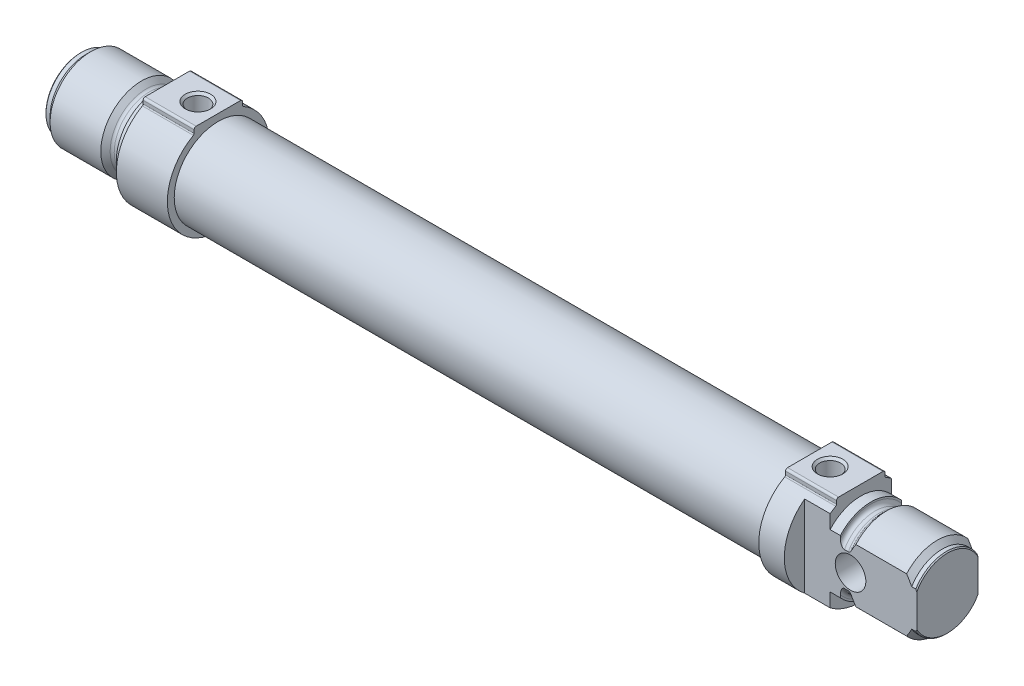
SolidWorks part; units mm, degrees
ref_plane "Ebene vorne" through (0, 0, 0) normal (0, 0, 1) x (1, 0, 0)
ref_plane "Ebene oben" through (0, 0, 0) normal (0, 1, 0) x (1, 0, 0)
ref_plane "Ebene rechts" through (0, 0, 0) normal (1, 0, 0) x (0, 0, -1)
sketch "Skizze1" plane through (0, 0, 0) normal (0, 0, 1) x (1, 0, 0)
  line L0 (0, 0) -> (0, 6.8)
  line L1 (0, 6.8) -> (0.2, 7)
  line L2 (0.2, 7) -> (1, 7)
  line L3 (1, 7) -> (2, 8)
  line L4 (2, 8) -> (11.95, 8)
  line L5 (11.95, 8) -> (12.8657, 7.0843)
  line L6 (13.4314, 6.85) -> (14.2, 6.85)
  line L7 (15, 7.65) -> (15, 8)
  line L8 (15, 8) -> (17, 8)
  line L9 (17, 8) -> (17, 0)
  line L10 (17, 0) -> (0, 0)
  line L11 (17, 0) -> (0, 0) construction
  arc A0 (12.8657, 7.0843) -> (13.4314, 6.85) centre (13.4314, 7.65) ccw
  arc A1 (14.2, 6.85) -> (15, 7.65) centre (14.2, 7.65) ccw
revolve "Rotation1" add sketch "Skizze1" angle 360 about L11 reverse direction yes
cosmetic thread "Gewindedarstellung1" parameters "D1"=10.87, "D2"=14.16
ref_plane "Ebene1" through (21.1, 0, 0) normal (1, 0, 0) x (0, 0, -1)
ref_plane "Ebene2" through (9, 0, 0) normal (1, 0, 0) x (0, 0, -1)
ref_plane "Ebene3" through (0, -11, 0) normal (0, 1, 0) x (1, 0, 0)
ref_plane "Ebene4" through (0, 11, 0) normal (0, 1, 0) x (1, 0, 0)
ref_plane "Ebene5" through (0, 0, 0) normal (0, 1, 0) x (1, 0, 0)
ref_plane "Ebene6" through (0, 0, 0) normal (0, 1, 0) x (1, 0, 0)
ref_plane "Ebene7" through (17, 0, 0) normal (1, 0, 0) x (0, 0, -1)
ref_plane "Ebene8" through (17, 0, 0) normal (1, 0, 0) x (0, 0, -1)
ref_plane "Ebene9" through (27, 0, 0) normal (1, 0, 0) x (0, 0, -1)
ref_plane "Ebene10" through (17, 0, 0) normal (1, 0, 0) x (0, 0, -1)
ref_plane "Ebene11" through (17, 0, 0) normal (1, 0, 0) x (0, 0, -1)
sketch "Skizze2" plane through (17, 0, 0) normal (1, 0, 0) x (0, 0, -1)
  line L0 (4.75, 8.9771) -> (4.75, 9.6)
  line L1 (4.35, 10) -> (-4.35, 10)
  line L2 (-4.75, 9.6) -> (-4.75, 8.9771)
  arc A0 (-4.9029, 8.7156) -> (4.9029, 8.7156) centre (0, 0) ccw
  arc A1 (4.9029, 8.7156) -> (4.75, 8.9771) centre (5.05, 8.9771) cw
  arc A2 (4.75, 9.6) -> (4.35, 10) centre (4.35, 9.6) ccw
  arc A3 (-4.35, 10) -> (-4.75, 9.6) centre (-4.35, 9.6) ccw
  arc A4 (-4.75, 8.9771) -> (-4.9029, 8.7156) centre (-5.05, 8.9771) cw
extrude "Aufsatz-Linear austragen1" add sketch "Skizze2" along normal blind 10
ref_plane "Ebene12" through (23, 0, 0) normal (1, 0, 0) x (0, 0, -1)
ref_plane "Ebene13" through (0, 0, 0) normal (0, 0, 1) x (1, 0, 0)
ref_plane "Ebene14" through (0, 0, -6.5) normal (0, 0, 1) x (1, 0, 0)
ref_plane "Ebene15" through (0, 0, 0) normal (0, 1, 0) x (1, 0, 0)
ref_plane "Ebene16" through (0, 5.5, 0) normal (0, 1, 0) x (1, 0, 0)
ref_plane "Ebene17" through (0, 0, -6.6) normal (0, 0, 1) x (1, 0, 0)
ref_plane "Ebene18" through (0, 0, 0) normal (0, 1, 0) x (1, 0, 0)
ref_plane "Ebene19" through (0, 5.5, 0) normal (0, 1, 0) x (1, 0, 0)
ref_plane "Ebene20" through (0, 6.4628, -1.1396) normal (0, 0.9848, -0.1736) x (1, 0, 0)
ref_plane "Ebene21" through (0, 4.9856, -0.8791) normal (0, 0.9848, -0.1736) x (1, 0, 0)
sketch "Skizze3" plane through (0, 0, 0) normal (0, 0, 1) x (1, 0, 0)
  line L0 (27, 0) -> (27, 8.65)
  line L1 (27, 8.65) -> (143, 8.65)
  line L2 (143, 8.65) -> (143, 0)
  line L3 (143, 0) -> (27, 0)
  line L4 (143, 0) -> (27, 0) construction
revolve "Rotation2" add sketch "Skizze3" angle 360 about L4 reverse direction yes
ref_plane "Ebene22" through (143, 0, 0) normal (1, 0, 0) x (0, 0, -1)
sketch "Skizze4" plane through (143, 0, 0) normal (1, 0, 0) x (0, 0, -1)
  line L0 (4.75, 8.9771) -> (4.75, 9.6)
  line L1 (4.35, 10) -> (-4.35, 10)
  line L2 (-4.75, 9.6) -> (-4.75, 8.9771)
  arc A0 (-4.9029, 8.7156) -> (4.9029, 8.7156) centre (0, 0) ccw
  arc A1 (4.9029, 8.7156) -> (4.75, 8.9771) centre (5.05, 8.9771) cw
  arc A2 (4.75, 9.6) -> (4.35, 10) centre (4.35, 9.6) ccw
  arc A3 (-4.35, 10) -> (-4.75, 9.6) centre (-4.35, 9.6) ccw
  arc A4 (-4.75, 8.9771) -> (-4.9029, 8.7156) centre (-5.05, 8.9771) cw
extrude "Aufsatz-Linear austragen2" add sketch "Skizze4" along normal blind 10
ref_plane "Ebene23" through (145.35, 0, 0) normal (1, 0, 0) x (0, 0, -1)
ref_plane "Ebene24" through (147, 0, 0) normal (1, 0, 0) x (0, 0, -1)
ref_plane "Ebene25" through (0, 0, 6.6) normal (0, 0, 1) x (1, 0, 0)
ref_plane "Ebene26" through (0, 0, 0) normal (0, 1, 0) x (1, 0, 0)
ref_plane "Ebene27" through (0, 5.5, 0) normal (0, 1, 0) x (1, 0, 0)
ref_plane "Ebene28" through (0, 6.4628, 1.1396) normal (0, 0.9848, 0.1736) x (1, 0, 0)
ref_plane "Ebene29" through (0, 4.9856, 0.8791) normal (0, 0.9848, 0.1736) x (1, 0, 0)
ref_plane "Ebene30" through (191, 0, 0) normal (1, 0, 0) x (0, 0, -1)
sketch "Skizze5" plane through (0, 0, 0) normal (0, 0, 1) x (1, 0, 0)
  line L0 (153, 0) -> (153, 8)
  line L1 (153, 8) -> (155, 8)
  line L2 (155, 8) -> (155, 7.65)
  line L3 (155.8, 6.85) -> (156.5686, 6.85)
  line L4 (157.1343, 7.0843) -> (158.05, 8)
  line L5 (158.05, 8) -> (168, 8)
  line L6 (168, 8) -> (169, 7)
  line L7 (169, 7) -> (169.8, 7)
  line L8 (169.8, 7) -> (170, 6.8)
  line L9 (170, 6.8) -> (170, 0)
  line L10 (170, 0) -> (153, 0)
  line L11 (170, 0) -> (153, 0) construction
  arc A0 (155, 7.65) -> (155.8, 6.85) centre (155.8, 7.65) ccw
  arc A1 (156.5686, 6.85) -> (157.1343, 7.0843) centre (156.5686, 7.65) ccw
revolve "Rotation3" add sketch "Skizze5" angle 360 about L11 reverse direction yes
cosmetic thread "Gewindedarstellung2" parameters "D1"=9.87, "D2"=14.16
ref_plane "Ebene31" through (181, 0, 0) normal (1, 0, 0) x (0, 0, -1)
ref_plane "Ebene32" through (191, 0, 0) normal (1, 0, 0) x (0, 0, -1)
ref_plane "Ebene33" through (191, 0, 0) normal (1, 0, 0) x (0, 0, -1)
sketch "Skizze6" plane through (0, 0, 0) normal (0, 1, 0) x (1, 0, 0)
  line L0 (148, 18) -> (148, 6)
  line L1 (148, 6) -> (170, 6)
  line L2 (170, 6) -> (170, -6)
  line L3 (170, -6) -> (148, -6)
  line L4 (148, -6) -> (148, -18)
  line L5 (148, -18) -> (182, -18)
  line L6 (182, -18) -> (182, 18)
  line L7 (182, 18) -> (148, 18)
extrude "Schnitt-Linear austragen1" cut sketch "Skizze6" along normal blind 10 and the other way blind 10
ref_plane "Ebene34" through (157, 0, 0) normal (1, 0, 0) x (0, 0, -1)
hole_wizard "Bohrung1" positions "Skizze8" profile "Skizze7" legacy
sketch "Skizze8" plane through (0, 0, -6) normal (0, 0, -1) x (-1, 0, 0)
  point P0 (-157, 0)
sketch "Skizze7" plane through (157, 0, -6) normal (1, 0, 0) x (0, 1, 0)
  line L0 (0, 0) -> (0, 12)
  line L1 (0, 12) -> (3, 12)
  line L2 (3, 12) -> (3, 0)
  line L3 (3, 0) -> (0, 0)
  line L4 (0, 110) -> (0, -10) construction
  dimension "Durchmesser" = 6
  dimension "Tiefe" = 12
hole_wizard "Bohrung2" positions "Skizze10" profile "Skizze9" legacy
sketch "Skizze10" plane through (0, 10, 0) normal (0, 1, 0) x (1, 0, 0)
  point P0 (23, 0)
sketch "Skizze9" plane through (23, 10, 0) normal (1, 0, 0) x (0, 0, 1)
  line L0 (0, 0) -> (0, 10)
  line L1 (0, 10) -> (2.067, 10)
  line L2 (2.067, 10) -> (2.067, 0.433)
  line L3 (2.067, 0.433) -> (2.5, 0)
  line L4 (2.5, 0) -> (0, 0)
  line L5 (0, -6.4453) -> (0, 115.525) construction
  line L6 (-2.067, 0.433) -> (-2.5, 0) construction
  dimension "Durchmesser" = 4.134
  dimension "Tiefe" = 10
  dimension "Senkwinkel1" = 90
  dimension "Senkdurchmesser3" = 5
cosmetic thread "Gewindedarstellung3" parameters "D1"=7, "D2"=5
hole_wizard "Bohrung3" positions "Skizze12" profile "Skizze11" legacy
sketch "Skizze12" plane through (0, 10, 0) normal (0, 1, 0) x (1, 0, 0)
  point P0 (147, 0)
sketch "Skizze11" plane through (147, 10, 0) normal (1, 0, 0) x (0, 0, 1)
  line L0 (0, 0) -> (0, 12.1934)
  line L1 (0, 12.1934) -> (2.067, 11)
  line L2 (2.067, 11) -> (2.067, 0.433)
  line L3 (2.067, 0.433) -> (2.5, 0)
  line L4 (2.5, 0) -> (0, 0)
  line L5 (0, -14.3089) -> (0, 102.4216) construction
  line L6 (0, 12.1934) -> (-2.067, 11) construction
  line L7 (-2.067, 0.433) -> (-2.5, 0) construction
  dimension "Durchmesser" = 4.134
  dimension "Tiefe" = 11
  dimension "Senkdurchmesser1" = 5
  dimension "Senkwinkel1" = 90
  dimension "Spitzenwinkel" = 120
cosmetic thread "Gewindedarstellung4" parameters "D1"=6, "D2"=5
sketch "Skizze13" plane through (0, 0, 0) normal (0, 0, 1) x (1, 0, 0)
  line L0 (-5, 0) -> (-5, 3)
  line L1 (-5, 3) -> (41.2, 3)
  line L2 (41.2, 3) -> (41.2, 8)
  line L3 (41.2, 8) -> (125.2, 8)
  line L4 (125.2, 8) -> (125.2, 0)
  line L5 (125.2, 0) -> (-5, 0)
  line L6 (125.2, 0) -> (-5, 0) construction
revolve "Schnitt-Rotation1" cut sketch "Skizze13" angle 360 about L6 reverse direction yes
ref_plane "Ebene35" through (-5, 0, 0) normal (1, 0, 0) x (0, 0, -1)
ref_plane "Ebene36" through (0, 10, 0) normal (0, 1, 0) x (1, 0, 0)
ref_plane "Ebene37" through (7, 0, 0) normal (1, 0, 0) x (0, 0, -1)
ref_plane "Ebene38" through (0, 0, 0) normal (1, 0, 0) x (0, 0, -1)
ref_plane "Ebene39" through (17, 0, 0) normal (1, 0, 0) x (0, 0, -1)
ref_plane "Ebene40" through (153, 0, 0) normal (1, 0, 0) x (0, 0, -1)
ref_plane "Ebene41" through (17, 0, 0) normal (1, 0, 0) x (0, 0, -1)
ref_plane "Ebene42" through (0, 10, 0) normal (0, 1, 0) x (1, 0, 0)
ref_plane "Ebene43" through (36.5, 0, 0) normal (1, 0, 0) x (0, 0, -1)
ref_plane "Ebene44" through (133.5, 0, 0) normal (1, 0, 0) x (0, 0, -1)
ref_plane "Ebene45" through (0, 0, 0) normal (0, 0, 1) x (1, 0, 0)
ref_plane "Ebene46" through (17, 0, 0) normal (1, 0, 0) x (0, 0, -1)
ref_plane "Ebene47" through (0, 10, 0) normal (0, 1, 0) x (1, 0, 0)
ref_plane "FDT_FRONT XY" through (17, 0, 0) normal (1, 0, 0) x (0, 0, -1)
ref_plane "FDT_FRONT XZ" through (0, 0, 0) normal (0, -1, 0) x (-1, 0, 0)
ref_plane "FDT_FRONT YZ" through (0, 0, 0) normal (0, 0, -1) x (-1, 0, 0)
ref_axis "FDT_FRONT X" through (17, 0, 80.9) along (0, 0, -1)
ref_axis "FDT_FRONT Y" through (17, -50, 0) along (0, 1, 0)
ref_axis "FDT_FRONT Z" through (80.9, 0, 0) along (-1, 0, 0)
sketch3d "FDT_FRONT"
  point P0 (17, 0, 0)
ref_plane "FDT_QSFRONT XY" through (0, 10, 0) normal (0, 1, 0) x (1, 0, 0)
ref_plane "FDT_QSFRONT XZ" through (23, 0, 0) normal (-1, 0, 0) x (0, 0, 1)
ref_plane "FDT_QSFRONT YZ" through (0, 0, 0) normal (0, 0, 1) x (1, 0, 0)
ref_axis "FDT_QSFRONT X" through (23, 10, -50) along (0, 0, 1)
ref_axis "FDT_QSFRONT Y" through (-80.9, 10, 0) along (1, 0, 0)
ref_axis "FDT_QSFRONT Z" through (23, 50, 0) along (0, -1, 0)
sketch3d "FDT_QSFRONT"
  point P0 (23, 10, 0)
ref_plane "FDT_QSREAR XY" through (0, 10, 0) normal (0, 1, 0) x (1, 0, 0)
ref_plane "FDT_QSREAR XZ" through (147, 0, 0) normal (-1, 0, 0) x (0, 0, 1)
ref_plane "FDT_QSREAR YZ" through (0, 0, 0) normal (0, 0, 1) x (1, 0, 0)
ref_axis "FDT_QSREAR X" through (147, 10, -50) along (0, 0, 1)
ref_axis "FDT_QSREAR Y" through (-80.9, 10, 0) along (1, 0, 0)
ref_axis "FDT_QSREAR Z" through (147, 50, 0) along (0, -1, 0)
sketch3d "FDT_QSREAR"
  point P0 (147, 10, 0)
ref_plane "FDT_REAR XY" through (153, 0, 0) normal (-1, 0, 0) x (0, 0, 1)
ref_plane "FDT_REAR XZ" through (0, 0, 0) normal (0, 1, 0) x (1, 0, 0)
ref_plane "FDT_REAR YZ" through (0, 0, 0) normal (0, 0, -1) x (-1, 0, 0)
ref_axis "FDT_REAR X" through (153, 0, 80.9) along (0, 0, -1)
ref_axis "FDT_REAR Y" through (153, 50, 0) along (0, -1, 0)
ref_axis "FDT_REAR Z" through (-80.9, 0, 0) along (1, 0, 0)
sketch3d "FDT_REAR"
  point P0 (153, 0, 0)
ref_plane "FDT_SMBR1 XY" through (36.5, 0, 0) normal (-1, 0, 0) x (0, 0, 1)
ref_plane "FDT_SMBR1 XZ" through (0, 0, 0) normal (0, -1, 0) x (-1, 0, 0)
ref_plane "FDT_SMBR1 YZ" through (0, 0, 0) normal (0, 0, 1) x (1, 0, 0)
ref_axis "FDT_SMBR1 X" through (36.5, 0, -80.9) along (0, 0, 1)
ref_axis "FDT_SMBR1 Y" through (36.5, -50, 0) along (0, 1, 0)
ref_axis "FDT_SMBR1 Z" through (-80.9, 0, 0) along (1, 0, 0)
sketch3d "FDT_SMBR1"
  point P0 (36.5, 0, 0)
ref_plane "FDT_SMBR2 XY" through (133.5, 0, 0) normal (-1, 0, 0) x (0, 0, 1)
ref_plane "FDT_SMBR2 XZ" through (0, 0, 0) normal (0, -1, 0) x (-1, 0, 0)
ref_plane "FDT_SMBR2 YZ" through (0, 0, 0) normal (0, 0, 1) x (1, 0, 0)
ref_axis "FDT_SMBR2 X" through (133.5, 0, -80.9) along (0, 0, 1)
ref_axis "FDT_SMBR2 Y" through (133.5, -50, 0) along (0, 1, 0)
ref_axis "FDT_SMBR2 Z" through (-80.9, 0, 0) along (1, 0, 0)
sketch3d "FDT_SMBR2"
  point P0 (133.5, 0, 0)
ref_plane "FDT_SWIVELAXIS XY" through (0, 0, 0) normal (0, 0, 1) x (1, 0, 0)
ref_plane "FDT_SWIVELAXIS XZ" through (0, 0, 0) normal (0, -1, 0) x (-1, 0, 0)
ref_plane "FDT_SWIVELAXIS YZ" through (157, 0, 0) normal (1, 0, 0) x (0, 0, -1)
ref_axis "FDT_SWIVELAXIS X" through (-80.9, 0, 0) along (1, 0, 0)
ref_axis "FDT_SWIVELAXIS Y" through (157, -50, 0) along (0, 1, 0)
ref_axis "FDT_SWIVELAXIS Z" through (157, 0, 80.9) along (0, 0, -1)
sketch3d "FDT_SWIVELAXIS"
  point P0 (157, 0, 0)
ref_plane "NUT XY" through (7, 0, 0) normal (1, 0, 0) x (0, 0, -1)
ref_plane "NUT XZ" through (0, 0, 0) normal (0, -1, 0) x (-1, 0, 0)
ref_plane "NUT YZ" through (0, 0, 0) normal (0, 0, -1) x (-1, 0, 0)
ref_axis "NUT X" through (7, 0, 80.9) along (0, 0, -1)
ref_axis "NUT Y" through (7, -50, 0) along (0, 1, 0)
ref_axis "NUT Z" through (80.9, 0, 0) along (-1, 0, 0)
sketch3d "NUT"
  point P0 (7, 0, 0)
ref_plane "ZR XY" through (0, 0, 0) normal (1, 0, 0) x (0, 0, -1)
ref_plane "ZR XZ" through (0, 0, 0) normal (0, -1, 0) x (-1, 0, 0)
ref_plane "ZR YZ" through (0, 0, 0) normal (0, 0, -1) x (-1, 0, 0)
ref_axis "ZR X" through (0, 0, 80.9) along (0, 0, -1)
ref_axis "ZR Y" through (0, -50, 0) along (0, 1, 0)
ref_axis "ZR Z" through (80.9, 0, 0) along (-1, 0, 0)
sketch3d "ZR"
  point P0 (0, 0, 0)
ref_plane "ZYL XY" through (17, 0, 0) normal (1, 0, 0) x (0, 0, -1)
ref_plane "ZYL XZ" through (0, 0, 0) normal (0, -1, 0) x (-1, 0, 0)
ref_plane "ZYL YZ" through (0, 0, 0) normal (0, 0, -1) x (-1, 0, 0)
ref_axis "ZYL X" through (17, 0, 80.9) along (0, 0, -1)
ref_axis "ZYL Y" through (17, -50, 0) along (0, 1, 0)
ref_axis "ZYL Z" through (80.9, 0, 0) along (-1, 0, 0)
sketch3d "ZYL"
  point P0 (17, 0, 0)
